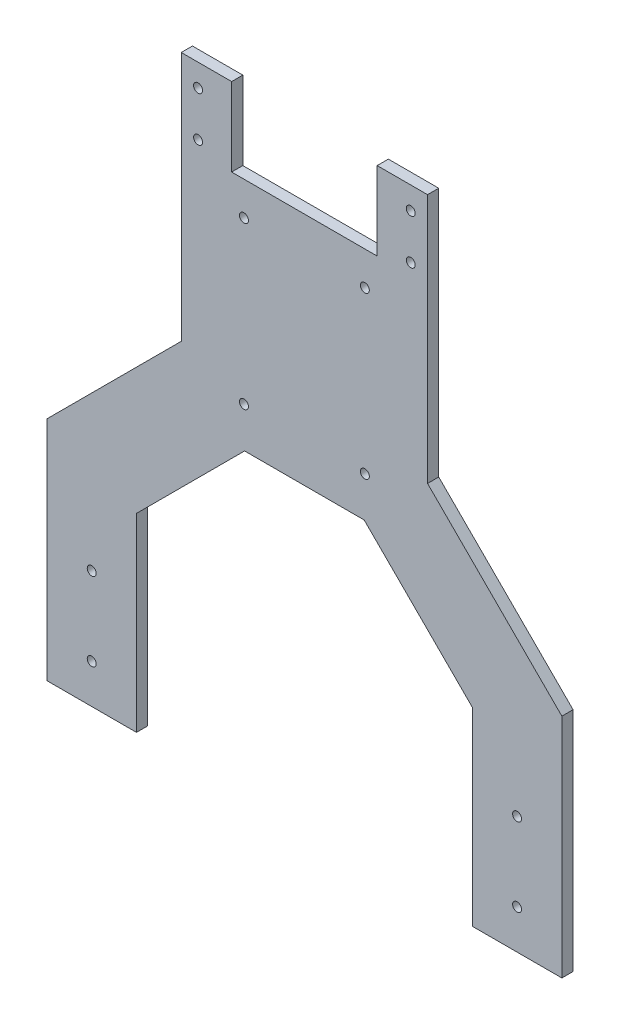
SolidWorks part; units mm, degrees
ref_plane "Front Plane" through (0, 0, 0) normal (0, 0, 1) x (1, 0, 0)
ref_plane "Top Plane" through (0, 0, 0) normal (0, 1, 0) x (1, 0, 0)
ref_plane "Right Plane" through (0, 0, 0) normal (1, 0, 0) x (0, 0, -1)
sketch "Sketch1" plane through (0, 0, 0) normal (0, 0, 1) x (1, 0, 0)
  line L1 (-100, -75) -> (100, -75)
  line L2 (-100, -75) -> (-100, 75)
  line L3 (-100, 75) -> (100, 75)
  line L4 (100, -75) -> (100, 75)
  line L5 (-100, -75) -> (100, 75) construction
  line L6 (-100, 75) -> (100, -75) construction
  line L8 (-47.5, 40) -> (47.5, 40) construction
  line L9 (0, 75) -> (0, -75) construction
  line L10 (-27, -52) -> (27, -52) construction
  line L11 (-27, -52) -> (-27, 20) construction
  line L12 (-27, 20) -> (27, 20) construction
  line L13 (27, -52) -> (27, 20) construction
  line L14 (-27, -52) -> (27, 20) construction
  line L15 (-27, 20) -> (27, -52) construction
  line L23 (-55, 70) -> (55, 70)
  line L24 (-55, 70) -> (-55, -70)
  line L25 (-55, -70) -> (55, -70)
  line L26 (55, 70) -> (55, -70)
  line L27 (-55, 70) -> (55, -70) construction
  line L28 (-55, -70) -> (55, 70) construction
  line L29 (-32.5, 70) -> (32.5, 70)
  line L30 (-32.5, 70) -> (-32.5, 35)
  line L31 (-32.5, 35) -> (32.5, 35)
  line L32 (32.5, 70) -> (32.5, 35)
  line L33 (-32.5, 70) -> (32.5, 35) construction
  line L34 (-32.5, 35) -> (32.5, 70) construction
  circle A2 centre (-47.5, 40) radius 2
  circle A3 centre (47.5, 40) radius 2
  circle A4 centre (-27, 20) radius 2
  circle A5 centre (27, 20) radius 2
  circle A6 centre (27, -52) radius 2
  circle A7 centre (-27, -52) radius 2
  circle A8 centre (-47.5, 60) radius 2
  circle A9 centre (47.5, 60) radius 2
  point P0 (0, 0)
  point P8 (0, 0)
  point P15 (0, 40)
  point P18 (0, -16)
  point P56 (0, 0)
  point P63 (0, 52.5)
  dimension "D3" = 4
  dimension "D4" = 20
  dimension "D5" = 4
  dimension "D8" = 4
  dimension "D1" = 150
  dimension "D2" = 200
  dimension "D6" = 72
  dimension "D7" = 54
  dimension "D14" = 30
  dimension "D15" = 140
  dimension "D16" = 110
  dimension "D17" = 95
  dimension "D18" = 20
  dimension "D19" = 35
  dimension "D20" = 65
extrude "Boss-Extrude1" add sketch "Sketch1" along normal blind 5 contours L23 L32 L31 L30 L24 L25 L26 A7 A6 A5 A4 A3 A2 region at (0, -9.3015, 0)
sketch "Sketch2" plane through (0, 0, 0) normal (0, 0, 1) x (1, 0, 0)
  line L0 (-55, -70) -> (-100.8579, -115.8579) construction
  line L1 (-55, 70) -> (-55, -70) construction
  line L2 (-55, -41.7157) -> (-115, -101.7157)
  line L3 (-26.7157, -70) -> (-86.7157, -130)
  line L4 (-55, -70) -> (55, -70) construction
  line L5 (-115, -101.7157) -> (-86.7157, -130)
  line L6 (-115, -101.7157) -> (-115, -203)
  line L7 (-75, -118.2843) -> (-75, -203)
  line L8 (-75, -203) -> (-115, -203)
  line L9 (0, 75) -> (0, -75) construction
  line L10 (-55, -41.7157) -> (-26.7157, -70)
  line L11 (-55, 70) -> (-55, -70) construction
  line L12 (-75, -203) -> (-115, -203) construction
  line L13 (-55, -70) -> (55, -70) construction
  line L14 (-55, 70) -> (-55, -70) construction
  circle A0 centre (-95, -150.5) radius 2
  circle A1 centre (-95, -185.5) radius 2
  point P30 (-95, -185.5)
  dimension "D5" = 4
  dimension "D6" = 4
  dimension "D1" = 135
  dimension "D2" = 40
  dimension "D3" = 40
  dimension "D4" = 75
extrude "Boss-Extrude2" add sketch "Sketch2" along normal blind 5 contours L8 L7 L3 L5 L6 | L10 L2 L5 L3 region at (-70.8579, -85.8579, 0) region at (-95.9289, -160.2024, 0)
mirror "Mirror1" about plane through (0, 0, 0) normal (1, 0, 0) of "Boss-Extrude2"
